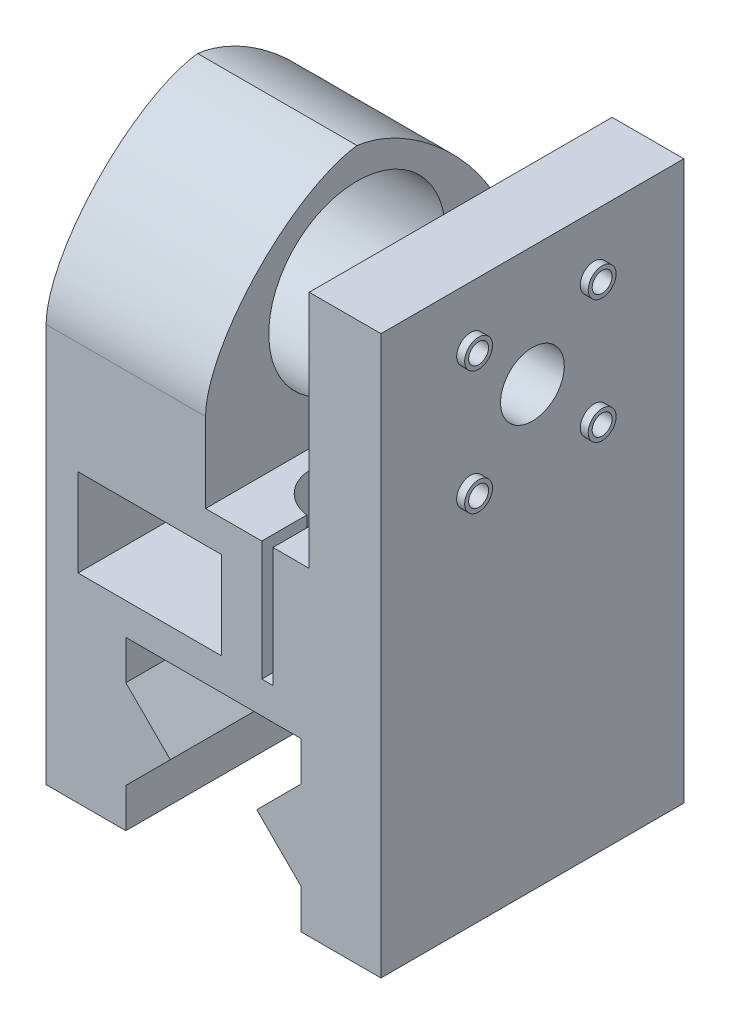
SolidWorks part; units mm, degrees
ref_plane "Front Plane" through (0, 0, 0) normal (0, 0, 1) x (1, 0, 0)
ref_plane "Top Plane" through (0, 0, 0) normal (0, 1, 0) x (1, 0, 0)
ref_plane "Right Plane" through (0, 0, 0) normal (1, 0, 0) x (0, 0, -1)
sketch "Sketch1" plane through (0, 0, 0) normal (0, 0, 1) x (1, 0, 0)
  line L0 (-11, 0) -> (11, 0)
  line L1 (11, 0) -> (11, -4.92)
  line L2 (11, -4.92) -> (5.42, -10.5)
  line L3 (5.42, -10.5) -> (11, -10.5) construction
  line L4 (11, -16.08) -> (5.42, -10.5)
  line L5 (11, -16.08) -> (11, -21)
  line L6 (0, 0) -> (0, -50000) construction
  line L7 (11, -21) -> (21, -21)
  line L8 (21, -21) -> (21, 19)
  line L9 (21, 19) -> (-21, 19)
  line L10 (-5.42, -10.5) -> (-11, -10.5) construction
  line L11 (-21, -21) -> (-21, 19)
  line L12 (-11, -21) -> (-21, -21)
  line L13 (-11, -16.08) -> (-11, -21)
  line L14 (-11, -16.08) -> (-5.42, -10.5)
  line L15 (-11, -4.92) -> (-5.42, -10.5)
  line L16 (-11, 0) -> (-11, -4.92)
  line L18 (-17, 15) -> (1, 15)
  line L19 (-17, 15) -> (-17, 4)
  line L20 (-17, 4) -> (1, 4)
  line L21 (1, 15) -> (1, 4)
  point P16 (0, 19)
  point P21 (0, 0)
  dimension "D1" = 11
  dimension "D2" = 4.92
  dimension "D3" = 7.8913
  dimension "D4" = 45
  dimension "D5" = 4.92
  dimension "D6" = 10
  dimension "D7" = 40
  dimension "D8" = 4
  dimension "D9" = 4
  dimension "D10" = 20
  dimension "D11" = 4
extrude "Boss-Extrude1" add sketch "Sketch1" along normal mid plane 38
sketch "Sketch2" plane through (0, 19, 0) normal (0, 1, 0) x (1, 0, 0)
  line L0 (21, -19) -> (-21, -19) construction
  line L1 (-21, 19) -> (-1, 19)
  line L2 (-21, 19) -> (-21, -19)
  line L3 (-21, -19) -> (-1, -19)
  line L4 (-1, 19) -> (-1, -19)
  dimension "D1" = 20
extrude "Boss-Extrude2" add sketch "Sketch2" along normal blind 30
fillet "Fillet2" radius 20 2 edges at (-11, 49, -19) (-11, 49, 19) conic rho 0.3
sketch "Sketch7" plane through (0, 19, 0) normal (0, 1, 0) x (1, 0, 0)
  line L0 (21, 19) -> (-1, 19) construction
  line L1 (12, 19) -> (21, 19)
  line L2 (12, 19) -> (12, -19)
  line L3 (12, -19) -> (21, -19)
  line L4 (21, 19) -> (21, -19)
  dimension "D1" = 9
extrude "Boss-Extrude6" add sketch "Sketch7" along normal blind 30
sketch "Sketch3" plane through (-21, 0, 0) normal (-1, 0, 0) x (0, 0, 1)
  line L0 (0, 0) -> (0, 44) construction
  circle A0 centre (0, 34) radius 11.075
  dimension "D1" = 22.15
  dimension "D2" = 34
extrude "Cut-Extrude1" cut sketch "Sketch3" against normal blind 31 and the other way through all
sketch "Sketch9" plane through (21, 0, 0) normal (1, 0, 0) x (0, 0, -1)
  line L0 (-19, 49) -> (19, 49) construction
  line L1 (-19, -21) -> (-19, 49) construction
  line L2 (19, -21) -> (19, 49) construction
  circle A0 centre (-7.75, 41.75) radius 1.75
  circle A1 centre (7.75, 41.75) radius 1.75
  circle A2 centre (-7.75, 26.25) radius 1.75
  circle A3 centre (7.75, 26.25) radius 1.75
  point P0 (-7.75, 41.75)
  point P2 (7.75, 41.75)
  point P4 (-7.75, 26.25)
  point P7 (7.75, 26.25)
  dimension "D1" = 3.5
  dimension "D2" = 3.5
  dimension "D3" = 3.5
  dimension "D4" = 3.5
  dimension "D5" = 7.25
  dimension "D6" = 11.25
  dimension "D7" = 11.25
  dimension "D8" = 15.5
ref_axis "Axis1" through (-1, 34, 0) along (-1, 0, 0)
sketch "Sketch5" plane through (0, 19, 0) normal (0, 1, 0) x (1, 0, 0)
  line L0 (12, 19) -> (-1, 19) construction
  line L1 (18.5, 19) -> (21, 19)
  line L2 (18.5, 19) -> (18.5, -19)
  line L3 (18.5, -19) -> (21, -19)
  line L4 (21, 19) -> (21, -19)
  line L5 (12, -19) -> (-1, -19) construction
  line L6 (21, -19) -> (21, 19) construction
  dimension "D1" = 2.5
extrude "Boss-Extrude3" add sketch "Sketch5" along normal blind 30
sketch "Sketch8" plane through (21, 0, 0) normal (1, 0, 0) x (0, 0, -1)
  line L0 (-19, 49) -> (19, 49) construction
  circle A0 centre (0, 34) radius 4
  dimension "D1" = 15
  dimension "D2" = 8
extrude "Cut-Extrude4" cut sketch "Sketch8" against normal through all
sketch "Sketch11" plane through (0, 19, 0) normal (0, 1, 0) x (1, 0, 0)
  line L0 (0, 0) -> (21, 0) construction
  line L1 (21, -19) -> (21, 19) construction
  line L2 (6.75, 19) -> (6.75, -19) construction
  line L3 (6.05, -13.3544) -> (6.05, -19)
  line L4 (7.45, -13.3544) -> (7.45, -19)
  line L5 (6.05, 19) -> (6.05, 13.3544)
  line L6 (7.45, 19) -> (7.45, 13.3544)
  line L7 (6.05, 19) -> (7.45, 19)
  line L8 (6.05, -19) -> (7.45, -19)
  line L9 (7.45, 2.6456) -> (7.45, -2.6456)
  line L10 (6.05, 2.6456) -> (6.05, -2.6456)
  circle A0 centre (6.75, 8) radius 4
  circle A1 centre (6.75, -8) radius 4
  arc A2 (7.45, 2.6456) -> (7.45, 13.3544) centre (6.75, 8) ccw
  arc A3 (7.45, -13.3544) -> (7.45, -2.6456) centre (6.75, -8) ccw
  arc A4 (6.05, -2.6456) -> (6.05, -13.3544) centre (6.75, -8) ccw
  arc A5 (6.05, 13.3544) -> (6.05, 2.6456) centre (6.75, 8) ccw
  dimension "D7" = 8
  dimension "D8" = 10.8
  dimension "D9" = 10.8
  dimension "D1" = 38
  dimension "D2" = 1.4
  dimension "D3" = 6.05
  dimension "D4" = 19
  dimension "D5" = 8
  dimension "D6" = 8
extrude "Cut-Extrude5" cut sketch "Sketch11" against normal blind 15
sketch "Sketch16" plane through (0, 19, 0) normal (0, 1, 0) x (1, 0, 0)
  line L0 (6.05, 2.6456) -> (6.05, -2.6456)
  line L1 (7.45, -2.6456) -> (7.45, 2.6456)
  arc A0 (6.05, 2.6456) -> (7.45, 2.6456) centre (6.75, 8) ccw
  arc A1 (7.45, -2.6456) -> (6.05, -2.6456) centre (6.75, -8) ccw
  point P1 (-17.8742, 8.5659)
  point P14 (8.12, 2.6456)
  dimension "D2" = 10.8
extrude "Boss-Extrude8" add sketch "Sketch16" against normal blind 15
extrude "Boss-Extrude7" add sketch "Sketch9" along normal blind 1
hole_wizard "Tap Drill for M3x0.5 Tap2" positions "3DSketch2" profile "Sketch15" hole size "M3x0.5" standard "ANSI Metric"
sketch3d "3DSketch2"
  line L0 (22, 41.75, 7.75) -> (21, 41.75, 7.75) construction
  line L1 (22, 41.75, -7.75) -> (21, 41.75, -7.75) construction
  line L2 (22, 26.25, -7.75) -> (21, 26.25, -7.75) construction
  line L3 (22, 26.25, 7.75) -> (21, 26.25, 7.75) construction
  point P0 (22, 41.75, 7.75)
  point P4 (-56.5655, 53.6952, 0)
  point P6 (-52.3499, 57.5798, 0)
  point P8 (22, 41.75, -7.75)
  point P12 (-34.3171, 58.8554, 0)
  point P14 (22, 26.25, -7.75)
  point P18 (22, 26.25, 7.75)
sketch "Sketch15" plane through (22, 41.75, 7.75) normal (0, 1, 0) x (0, 0, -1)
  line L0 (0, 0) -> (0, 8)
  line L1 (0, 8) -> (1.25, 8)
  line L2 (1.25, 8) -> (1.25, 0)
  line L5 (1.25, 0) -> (0, 0)
  line L10 (0, 8) -> (-1.25, 8) construction
  line L11 (0, -6.35) -> (0, 107.95) construction
  dimension "Hole Dia." = 2.5
  dimension "Hole Depth" = 8
  dimension "Drill Angle" = 180
